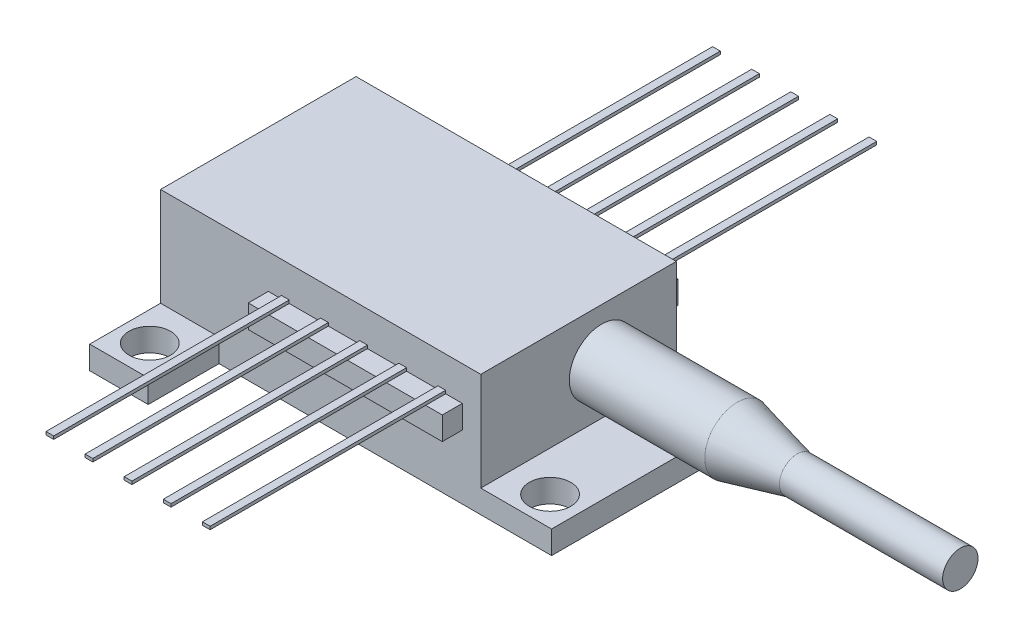
SolidWorks part; units mm, degrees
ref_plane "Front Plane" through (0, 0, 0) normal (0, 0, 1) x (1, 0, 0)
ref_plane "Top Plane" through (0, 0, 0) normal (0, 1, 0) x (1, 0, 0)
ref_plane "Right Plane" through (0, 0, 0) normal (1, 0, 0) x (0, 0, -1)
sketch "Sketch1" plane through (0, 0, 0) normal (0, 1, 0) x (1, 0, 0)
  line L1 (-10.4, -6.35) -> (10.4, -6.35)
  line L2 (-10.4, -6.35) -> (-10.4, 6.35)
  line L3 (-10.4, 6.35) -> (10.4, 6.35)
  line L4 (10.4, -6.35) -> (10.4, 6.35)
  line L5 (-10.4, -6.35) -> (10.4, 6.35) construction
  line L6 (-10.4, 6.35) -> (10.4, -6.35) construction
  point P0 (0, 0)
  dimension "D1" = 12.7
  dimension "D2" = 20.8
extrude "Boss-Extrude1" add sketch "Sketch1" along normal blind 6.4
sketch "Sketch3" plane through (0, 0, 0) normal (0, -1, 0) x (1, 0, 0)
  line L0 (-10.4, 6.35) -> (10.4, 6.35) construction
  line L1 (-10.4, 10.95) -> (-6.6, 10.95)
  line L2 (-10.4, 10.95) -> (-10.4, -10.95)
  line L3 (-10.4, 0) -> (15, 0) construction
  line L4 (15, 6.35) -> (15, -6.35)
  line L5 (-6.6, -6.35) -> (15, -6.35)
  line L6 (-6.6, 10.95) -> (-6.6, 6.35)
  line L7 (-6.6, 6.35) -> (15, 6.35)
  line L8 (-6.6, -10.95) -> (-6.6, -6.35)
  line L9 (-10.4, -10.95) -> (-6.6, -10.95)
  dimension "D1" = 25.4
  dimension "D2" = 10.95
  dimension "D3" = 3.8
extrude "Boss-Extrude2" add sketch "Sketch3" along normal blind 1.5
sketch "Sketch5" plane through (0, -1.5, 0) normal (0, -1, 0) x (1, 0, 0)
  line L0 (15, -6.35) -> (15, 6.35) construction
  line L1 (-10.4, 10.95) -> (-10.4, 6.35) construction
  circle A0 centre (-8.5, 8.95) radius 1.35
  circle A1 centre (13, 4.45) radius 1.35
  dimension "D1" = 2.7
  dimension "D2" = 4.45
  dimension "D3" = 2
  dimension "D4" = 8.95
  dimension "D5" = 1.9
extrude "Cut-Extrude1" cut sketch "Sketch5" against normal through all
mirror "Mirror3" about plane through (0, 0, 0) normal (0, 0, 1) of "Cut-Extrude1"
sketch "Sketch6" plane through (-10.4, 0, 0) normal (-1, 0, 0) x (0, 0, 1)
  line L0 (6.35, 6.4) -> (6.35, 0) construction
  line L1 (10.95, -1.5) -> (-10.95, -1.5) construction
  point P0 (1.85, 3.3)
  dimension "D1" = 4.5
  dimension "D2" = 4.8
ref_point "laser_out"
ref_axis "laser" through (-10.4, 3.3, 1.85) along (-1, 0, 0)
sketch "Sketch7" plane through (10.4, 0, 0) normal (1, 0, 0) x (0, 0, -1)
  line L0 (6.35, 6.4) -> (6.35, 0) construction
  line L1 (6.35, -1.5) -> (-6.35, -1.5) construction
  point P0 (1.5, 3.2)
  dimension "D1" = 4.85
  dimension "D2" = 4.7
ref_point "fiber_out"
ref_plane "Plane2" through (0, 3.2, 0) normal (0, -1, 0) x (-1, 0, 0)
ref_axis "fiber" through (10.4, 3.2, -1.5) along (1, 0, 0)
sketch "Sketch11" plane through (0, 3.2, 0) normal (0, -1, 0) x (-1, 0, 0)
  line L0 (-10.4, 1.5) -> (-10.4, 3.6)
  line L1 (-10.4, -6.35) -> (-10.4, 6.35) construction
  line L2 (-10.4, 3.6) -> (-19.2, 3.6)
  line L3 (-19.2, 3.6) -> (-23.1, 2.65)
  line L4 (-23.1, 2.65) -> (-33.7, 2.65)
  line L5 (-33.7, 2.65) -> (-33.7, 1.5)
  line L6 (-10.4, 1.5) -> (-61.1766, 1.5) construction
  line L7 (-33.7, 1.5) -> (-10.4, 1.5)
  line L8 (-10.4, -6.35) -> (-10.4, 6.35) construction
  dimension "D1" = 1.15
  dimension "D2" = 2.1
  dimension "D3" = 8.8
  dimension "D4" = 12.7
  dimension "D5" = 23.3
revolve "Revolve1" add sketch "Sketch11" angle 360 about axis through (10.4, 3.2, -1.5) along (1, 0, 0)
ref_plane "Plane1" through (0, 2.665, 0) normal (0, -1, 0) x (-1, 0, 0)
sketch "Sketch9" plane through (0, 2.665, 0) normal (0, -1, 0) x (-1, 0, 0)
  line L0 (10.4, -6.35) -> (-10.4, -6.35) construction
  line L1 (3.4, -6.35) -> (-9.2, -6.35)
  line L2 (3.4, -6.35) -> (3.4, -7.65)
  line L3 (3.4, -7.65) -> (-9.2, -7.65)
  line L4 (-9.2, -6.35) -> (-9.2, -7.65)
  line L6 (10.4, 6.35) -> (10.4, -6.35) construction
  line L7 (-10.4, -6.35) -> (-10.4, 6.35) construction
  dimension "D1" = 7.65
  dimension "D2" = 1.2
  dimension "D3" = 7
extrude "Boss-Extrude4" add sketch "Sketch9" against normal blind 1.5
sketch "Sketch10" plane through (0, 4.165, 0) normal (0, 1, 0) x (1, 0, 0)
  line L0 (-3.4, -6.35) -> (9.2, -6.35) construction
  line L1 (7.62, -6.35) -> (8.12, -6.35)
  line L2 (7.62, -6.35) -> (7.62, -21.65)
  line L3 (7.62, -21.65) -> (8.12, -21.65)
  line L4 (8.12, -6.35) -> (8.12, -21.65)
  line L5 (7.87, -6.35) -> (7.87, -21.65) construction
  line L6 (10.4, -6.35) -> (10.4, 6.35) construction
  dimension "D1" = 0.5
  dimension "D2" = 21.65
  dimension "D3" = 2.53
extrude "Boss-Extrude5" add sketch "Sketch10" along normal blind 0.2
pattern_linear "LPattern1" count 5 spacing 2.54 along (-1, 0, 0) of "Boss-Extrude5"
mirror "Mirror2" about plane through (0, 0, 0) normal (0, 0, 1) of "Boss-Extrude4", "Boss-Extrude5", "LPattern1"
